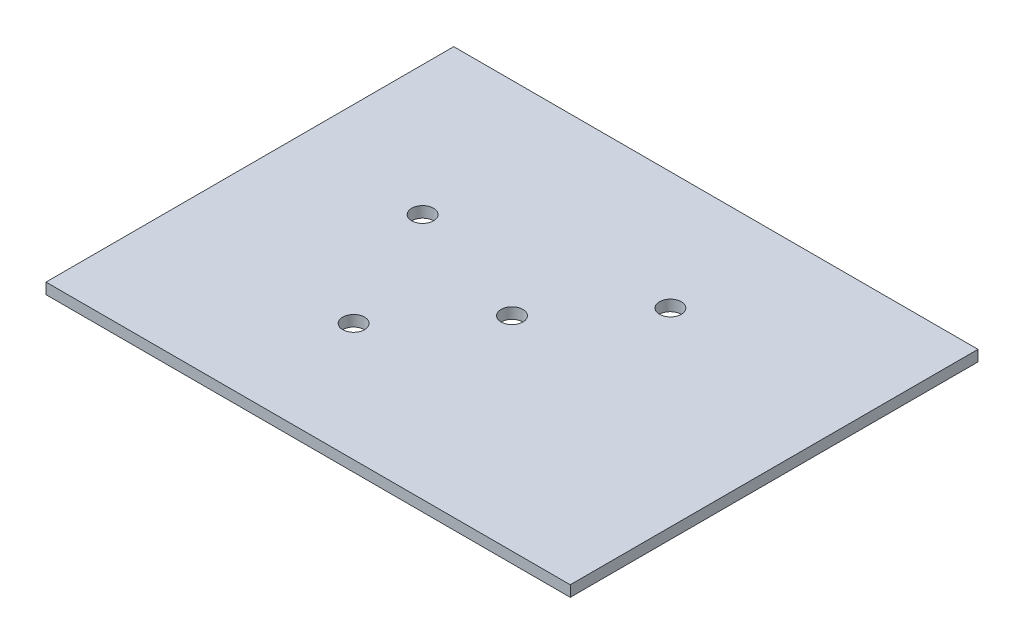
SolidWorks part; units mm, degrees
material "Oak"
ref_plane "Front Plane" through (0, 0, 0) normal (0, 0, 1) x (1, 0, 0)
ref_plane "Top Plane" through (0, 0, 0) normal (0, 1, 0) x (1, 0, 0)
ref_plane "Right Plane" through (0, 0, 0) normal (1, 0, 0) x (0, 0, -1)
sketch "Sketch1" plane through (0, 0, 0) normal (0, 1, 0) x (1, 0, 0)
  line L0 (558.8, 99.2707) -> (461.5124, 17.6367)
  line L1 (-558.8, -177.8) -> (558.8, -177.8)
  line L2 (-558.8, 177.8) -> (558.8, 177.8)
  line L3 (558.8, -177.8) -> (558.8, 177.8)
  line L4 (-558.8, -177.8) -> (558.8, 177.8) construction
  line L5 (-558.8, 177.8) -> (558.8, -177.8) construction
  line L6 (-228.6, 177.8) -> (228.6, 177.8)
  line L7 (-228.6, -177.8) -> (228.6, -177.8)
  line L8 (228.6, 177.8) -> (228.6, -177.8)
  line L9 (-228.6, 177.8) -> (228.6, -177.8) construction
  line L10 (-228.6, -177.8) -> (228.6, 177.8) construction
  line L11 (228.6, -177.8) -> (558.8, 99.2707)
  line L12 (-228.6, 177.8) -> (-228.6, -177.8)
  point P4 (0, 0)
extrude "Boss-Extrude1" add sketch "Sketch1" along normal blind 9.525 contours L8 L11 L0 L3 L2 region at (358.5765, 0, -54.5316)
extrude "Boss-Extrude2" add sketch "Sketch1<4>" along normal blind 9.525 contours L11 L1 L3 L0 region at (448.7333, 0, 85.4431)
sketch "Sketch1<4>" plane through (0, 0, 0) normal (0, 1, 0) x (1, 0, 0) same geometry as "Sketch1"
sketch "Sketch3" plane through (0, 0, 0) normal (0, -1, 0) x (1, 0, 0)
  line L0 (558.8, 177.8) -> (228.6, -177.8)
  line L1 (228.6, 177.8) -> (558.8, -177.8)
  line L2 (228.6, -177.8) -> (393.7, -177.8)
  line L3 (228.6, -177.8) -> (558.8, -177.8) construction
  line L4 (393.7, 0) -> (393.7, -177.8)
  line L5 (393.7, 0) -> (228.6, 0)
  line L6 (228.6, -177.8) -> (228.6, 177.8) construction
  line L7 (393.7, 0) -> (558.8, 0)
  line L8 (228.6, 0) -> (228.6, 177.8)
  line L9 (558.8, 177.8) -> (558.8, -177.8) construction
  line L10 (311.15, 44.45) -> (311.15, 0)
  line L15 (311.15, -88.9) -> (393.7, -88.9)
  line L18 (476.25, 88.9) -> (311.15, 88.9)
  line L19 (311.15, 88.9) -> (311.15, 44.45)
  line L25 (228.6, 177.8) -> (558.8, 177.8) construction
  line L33 (311.15, -177.8) -> (476.25, 177.8)
  circle A0 centre (393.7, 0) radius 9.525
  circle A1 centre (278.3073, -37.4464) radius 9.525
  circle A2 centre (330.442, 74.8683) radius 9.525
  circle A3 centre (456.958, -74.8683) radius 9.525
  dimension "D1" = 162.026
  dimension "D2" = 137.121
  dimension "D3" = 137.121
  dimension "D4" = 98.0145
  dimension "D5" = 65.095
extrude "Cut-Extrude6" cut sketch "Sketch3" along direction (0, 1, 0) on the side against the normal through all contours A1 | L1 A2 | L1 A2 | L1 A0 L5 | L5 A0 L0 | L0 A0 L33 | L33 A0 L4 | L4 A0 L1 | L1 A0 L7 | L7 A0 L0 | L0 A0 L33 | L33 A0 L1 | L1 A3 | L1 A3 region at (461.8055, 0, -70.367) region at (455.7034, 0, -76.0333) region at (388.042, 0, -2.4673) region at (390.1736, 0, -5.2495) region at (397.2264, 0, 5.2495) region at (388.042, 0, 2.4673) region at (399.358, 0, -2.4673) region at (395.9673, 0, -5.7736) region at (399.358, 0, 2.4673) region at (392.3415, 0, -6.1519) region at (392.7649, 0, 5.9126) region at (325.5945, 0, 70.367) region at (331.6966, 0, 76.0333) region at (278.3073, 0, -37.4464)
sketch "Sketch4" plane through (0, 0, 0) normal (0, -1, 0) x (1, 0, 0)
  line L1 (558.8, 177.8) -> (622.3, 177.8)
  line L2 (558.8, 177.8) -> (558.8, -177.8)
  line L3 (558.8, -177.8) -> (622.3, -177.8)
  line L4 (228.6, 177.8) -> (228.6, -177.8)
  line L5 (228.6, -177.8) -> (558.8, -177.8)
  line L6 (558.8, -177.8) -> (558.8, 177.8)
  line L7 (558.8, 177.8) -> (228.6, 177.8)
  line L8 (228.6, 177.8) -> (228.6, -177.8)
  line L9 (228.6, -177.8) -> (558.8, -177.8)
  line L10 (558.8, -177.8) -> (558.8, 177.8)
  line L11 (558.8, 177.8) -> (228.6, 177.8)
  line L12 (622.3, 177.8) -> (622.3, -177.8)
  line L13 (228.6, 177.8) -> (165.1, 177.8)
  line L14 (228.6, 177.8) -> (228.6, -177.8)
  line L15 (228.6, -177.8) -> (165.1, -177.8)
  line L16 (165.1, 177.8) -> (165.1, -177.8)
  line M9 (228.6, 177.8) -> (228.6, -177.8)
  line M11 (558.8, -177.8) -> (558.8, 177.8)
  dimension "D1" = 0
extrude "Boss-Extrude3" add sketch "Sketch4" against normal blind 9.525 contours L13 L16 L15 M9 | L12 L1 L3 M11 region at (590.55, 0, 0) region at (196.85, 0, 0)
